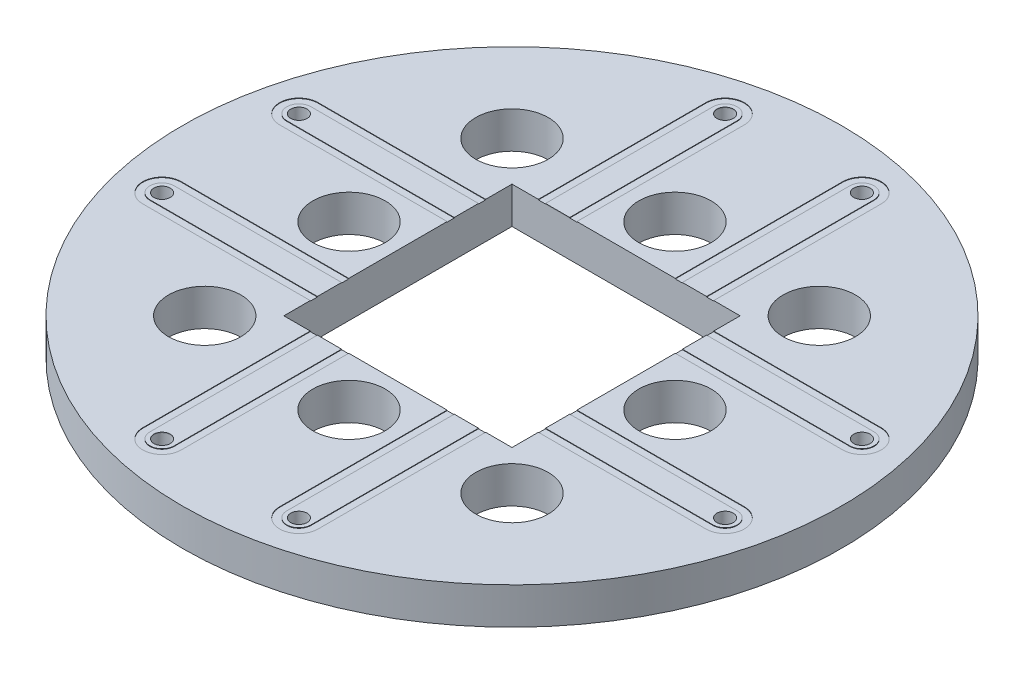
SolidWorks part; units mm, degrees
material "Ceramic Porcelain"
ref_plane "Front Plane" through (0, 0, 0) normal (0, 0, 1) x (1, 0, 0)
ref_plane "Top Plane" through (0, 0, 0) normal (0, 1, 0) x (1, 0, 0)
ref_plane "Right Plane" through (0, 0, 0) normal (1, 0, 0) x (0, 0, -1)
ref_axis "Y Axis" through (0, 0.0762, 0) along (0, -1, 0)
sketch "Boday Sketch" plane through (0, 0, 0) normal (0, 1, 0) x (1, 0, 0)
  circle A0 centre (0, 0) radius 11.557
  dimension "D1" = 23.114
extrude "Body" add sketch "Boday Sketch" against normal blind 1.27
sketch "Copper Sketch" plane through (0, 0, 0) normal (0, 1, 0) x (1, 0, 0)
  circle A0 centre (0, 0) radius 11.557
  dimension "D1" = 23.114
extrude "Copper" add sketch "Copper Sketch" along normal blind 0.0175
sketch "IO Hole Positions" plane through (0, 0, 0) normal (0, 1, 0) x (1, 0, 0)
  line L0 (-11.557, 0) -> (11.557, 0) construction
  circle A1 centre (0, 0) radius 11.557 construction
  point P1 (-2.4, 9.8725)
  point P8 (-2.4, -9.8725)
  dimension "D2" = 2.4
sketch "Gap" plane through (0, 0, 0) normal (0, 1, 0) x (1, 0, 0)
  line L10 (-3.075, 9.8725) -> (-3.075, -9.8725)
  line L11 (-11.557, 0) -> (11.557, 0) construction
  line L12 (-3.075, 0) -> (-1.725, 0) construction
  line L13 (-1.725, -9.8725) -> (-1.725, 9.8725)
  arc A5 (-1.725, 9.8725) -> (-3.075, 9.8725) centre (-2.4, 9.8725) ccw
  arc A6 (-1.725, -9.8725) -> (-3.075, -9.8725) centre (-2.4, -9.8725) cw
  dimension "D1" = 0.675
sketch "Center Sketch" plane through (0, 0, 0) normal (0, 1, 0) x (1, 0, 0)
  line L6 (-2.825, 9.8725) -> (-2.825, -9.8725)
  line L7 (-11.557, 0) -> (11.557, 0) construction
  line L8 (-2.825, 0) -> (-1.975, 0) construction
  line L9 (-1.975, -9.8725) -> (-1.975, 9.8725)
  arc A3 (-1.975, 9.8725) -> (-2.825, 9.8725) centre (-2.4, 9.8725) ccw
  arc A4 (-1.975, -9.8725) -> (-2.825, -9.8725) centre (-2.4, -9.8725) cw
  dimension "D1" = 0.425
extrude "Gap Cut" cut sketch "Gap" along normal through all
extrude "Center" add sketch "Center Sketch" along normal blind 0.0175 separate body
sketch "IO Hole Sketch" plane through (0, 0, 0) normal (0, 1, 0) x (1, 0, 0)
  circle A1 centre (-2.4, 9.8725) radius 0.287
  circle A3 centre (-2.4, -9.8725) radius 0.287
  dimension "D1" = 0.574
  dimension "D2" = 0.574
extrude "IO Hole" cut sketch "IO Hole Sketch" against normal through all and the other way through all
pattern_circular "Gap Cuts" count 4 over 360 about axis through (0, 0.0762, 0) along (0, -1, 0) of "Gap Cut"
pattern_circular "Centers" count 4 over 360 about axis through (0, 0.0762, 0) along (0, -1, 0) of "Center"
pattern_circular "IO Holes" count 4 over 360 about axis through (0, 0.0762, 0) along (0, -1, 0) of "IO Hole"
sketch "Pocket Sketch" plane through (0, 0, 0) normal (0, 1, 0) x (1, 0, 0)
  line L1 (-4, -4) -> (4, -4)
  line L2 (-4, -4) -> (-4, 4)
  line L3 (-4, 4) -> (4, 4)
  line L4 (4, -4) -> (4, 4)
  line L5 (-4, -4) -> (4, 4) construction
  line L6 (-4, 4) -> (4, -4) construction
  point P0 (0, 0)
  dimension "D1" = 8
  dimension "D2" = 8
extrude "Pocket" cut sketch "Pocket Sketch" against normal through all and the other way through all
sketch "Posts" plane through (0, 0, 0) normal (0, 1, 0) x (1, 0, 0)
  circle A0 centre (0, 5.715) radius 1.27
  circle A8 centre (-5.3882, 5.3882) radius 1.27
  point P0 (0, 5.715)
  point P4 (-5.3882, 5.3882)
  dimension "D2" = 2.54
  dimension "D4" = 2.54
  dimension "D1" = 5.715
  dimension "D3" = 7.62
  dimension "D5" = 5.715
extrude "Post Cut" cut sketch "Posts" against normal through all and the other way through all
pattern_circular "Post Cuts" count 4 over 360 about axis through (0, 0.0762, 0) along (0, -1, 0) of "Post Cut"
equation "\"mount_d\"= 0.91in"
equation "\"dieletric_h\"= 0.05in"
equation "\"D1@Boday Sketch\" = \"mount_d\""
equation "\"D1@Body\" = \"dieletric_h\""
equation "\"screw_inner_r\"= 0.415in"
equation "\"io_r\"= 0.4in"
equation "\"io_hole_d\"= 0.574mm"
equation "\"W\"= 0.85mm"
equation "\"G\"= 0.25mm"
equation "\"copper_t\"= 17.5um"
equation "\"silicon_size\"= 8mm"
equation "\"D1@Center\" = \"copper_t\""
equation "\"D1@Copper\"=\"copper_t\""
equation "\"D1@Pocket Sketch\" = \"silicon_size\""
equation "\"D2@Pocket Sketch\" = \"silicon_size\""
equation "\"post_r1\"= 0.225in"
equation "\"post_r2\"= 0.3in"
equation "\"D1@Posts\"=\"post_r1\""
equation "\"post_size\"= 0.1in"
equation "\"D2@Posts\"=\"post_size\""
equation "\"D3@Posts\"=\"post_r2\""
equation "\"D4@Posts\"=\"post_size\""
equation "\"io_x\"= 2.4mm"
equation "\"D1@IO Hole Positions\"=\"io_r\""
equation "\"D2@IO Hole Positions\"=\"io_x\""
equation "\"D1@IO Hole Sketch\"=\"io_hole_d\""
equation "\"D2@IO Hole Sketch\"=\"io_hole_d\""
equation "\"D1@Gap\"= \"W\" / 2 + \"G\""
equation "\"D1@Center Sketch\"=\"W\" / 2"
equation "\"D5@Posts\"=\"post_r1\""
